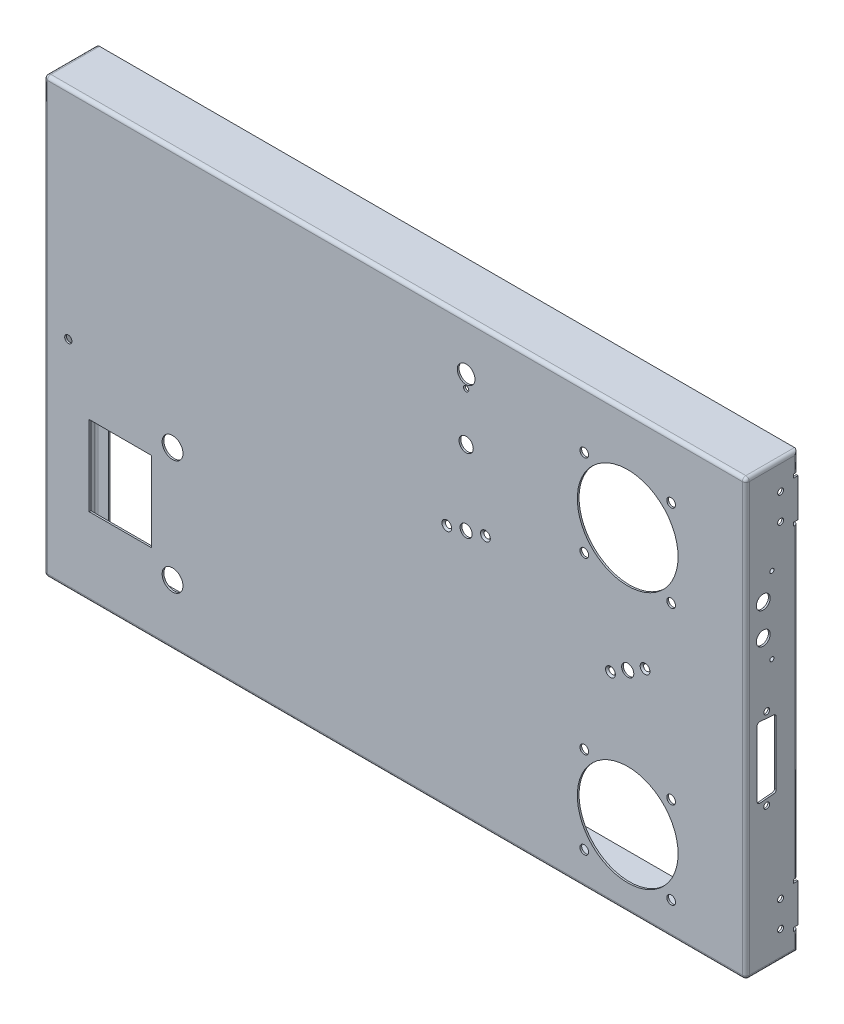
SolidWorks part; units mm, degrees
ref_plane "Спереди" through (0, 0, 0) normal (0, 0, 1) x (1, 0, 0)
ref_plane "Сверху" through (0, 0, 0) normal (0, 1, 0) x (1, 0, 0)
ref_plane "Справа" through (0, 0, 0) normal (1, 0, 0) x (0, 0, -1)
sketch "Эскиз1" plane through (0, 0, 0) normal (0, 0, 1) x (1, 0, 0)
  line L0 (-61.3968, 0) -> (71.7779, 0) construction
  line L1 (0, 39.2999) -> (0, -30.4018) construction
  line L2 (134, 171.767) -> (134, -149.1814) construction
  line L3 (-202, -125) -> (202, -125)
  line L4 (-202, -125) -> (-202, 125)
  line L5 (-202, 125) -> (202, 125)
  line L6 (202, -125) -> (202, 125)
  line L7 (38.5428, 67) -> (176.6445, 67) construction
  line L8 (42.9621, -81) -> (166.1488, -81) construction
  line L9 (-128, 10.4311) -> (-128, -100.5771) construction
  line L10 (117.5567, -13.5525) -> (151.8886, 6.269) construction
  line L11 (118.3296, -4) -> (150.7938, -4) construction
  line L12 (41, 146.2772) -> (41, -144.7589) construction
  line L13 (18.8787, 13.0871) -> (67.6345, 26.1512) construction
  line L14 (21.7516, 19) -> (64.0231, 19) construction
  line L15 (-220.928, 0) -> (-152.2094, 0) construction
  line L17 (-176, -80) -> (-140, -80)
  line L18 (-176, -80) -> (-176, -34)
  line L19 (-176, -34) -> (-140, -34)
  line L20 (-140, -80) -> (-140, -34)
  circle A0 centre (134, -4) radius 3.5
  circle A1 centre (-128, -24) radius 6
  circle A2 centre (-128, -90) radius 6
  circle A3 centre (134, 67) radius 29
  circle A4 centre (109, 92) radius 2.5
  circle A5 centre (109, 42) radius 2.5
  circle A6 centre (159, 42) radius 2.5
  circle A7 centre (159, 92) radius 2.5
  circle A8 centre (124.0664, -9.7942) radius 1.8
  circle A9 centre (143.985, 1.7058) radius 1.8
  circle A10 centre (134, -81) radius 29
  circle A11 centre (109, -56) radius 2.5
  circle A12 centre (159, -56) radius 2.5
  circle A13 centre (159, -106) radius 2.5
  circle A14 centre (109, -106) radius 2.5
  circle A15 centre (41, 97) radius 5.1
  circle A16 centre (41, 89.8) radius 1.5
  circle A17 centre (41, 62) radius 4.1
  circle A18 centre (41, 19) radius 3.5
  circle A19 centre (29.8882, 16.0371) radius 1.8
  circle A20 centre (52.1045, 21.99) radius 1.8
  circle A21 centre (-188, 0) radius 2.1
  dimension "D6" = 129
  dimension "D8" = 66
  dimension "D10" = 74
  dimension "D11" = 58
  dimension "D12" = 50
  dimension "D13" = 50
  dimension "D14" = 5
  dimension "D15" = 7
  dimension "D17" = 23
  dimension "D18" = 11.5
  dimension "D19" = 3.6
  dimension "D20" = 58
  dimension "D21" = 5
  dimension "D22" = 50
  dimension "D23" = 50
  dimension "D24" = 12
  dimension "D25" = 28
  dimension "D26" = 7.2
  dimension "D27" = 10.2
  dimension "D28" = 3
  dimension "D29" = 35
  dimension "D30" = 8.2
  dimension "D31" = 43
  dimension "D33" = 7
  dimension "D34" = 23
  dimension "D35" = 11.5
  dimension "D36" = 3.6
  dimension "D37" = 14
  dimension "D38" = 4.2
  dimension "D1" = 404
  dimension "D2" = 250
  dimension "D3" = 68
  dimension "D5" = 58
  dimension "D7" = 44
  dimension "D9" = 35
  dimension "D16" = 30
  dimension "D32" = 15
  dimension "D39" = 36
  dimension "D40" = 46
  dimension "D41" = 26
  dimension "D42" = 45
extrude "Вытянуть1" add sketch "Эскиз1" along normal blind 1
sketch "Эскиз2" plane through (0, 0, 1) normal (0, 0, 1) x (1, 0, 0)
  line L0 (-202, -125) -> (202, -125) construction
  line L1 (202, 125) -> (201, 125)
  line L2 (202, 125) -> (202, -125)
  line L3 (202, -125) -> (201, -125)
  line L4 (201, 125) -> (201, -125)
  line L5 (0, 139.8608) -> (0, -147.4853) construction
  line L6 (202, 125) -> (-202, 125) construction
  line L7 (-202, -125) -> (-201, -125)
  line L8 (-202, -125) -> (-202, 125)
  line L9 (-202, 125) -> (-201, 125)
  line L10 (-201, -125) -> (-201, 125)
  dimension "D1" = 1
  dimension "D2" = 1
extrude "Вытянуть2" add sketch "Эскиз2" against normal blind 30
sketch "Эскиз3" plane through (-202, 0, 0) normal (-1, 0, 0) x (0, 0, 1)
  line L0 (1, -125) -> (-29, -125) construction
  line L1 (-29, 125) -> (-28, 125)
  line L2 (-29, 125) -> (-29, -125)
  line L3 (-29, -125) -> (-28, -125)
  line L4 (-28, 125) -> (-28, -125)
  line L5 (27.4308, 0) -> (-48.9434, 0) construction
  line L7 (-29, 125) -> (-29, -125) construction
  dimension "D2" = 1
extrude "Вытянуть3" add sketch "Эскиз3" against normal blind 8
sketch "Эскиз4" plane through (202, 0, 0) normal (1, 0, 0) x (0, 0, -1)
  line L0 (28, -125) -> (28, 125) construction
  line L1 (28, -125) -> (28, 125)
  line L2 (29, -125) -> (28, -125) construction
  line L3 (29, -125) -> (28, -125)
  line L4 (28, 125) -> (29, 125) construction
  line L5 (28, 125) -> (29, 125)
  line L6 (29, -125) -> (29, 125) construction
  line L7 (29, -125) -> (29, 125)
extrude "Вытянуть4" add sketch "Эскиз4" against normal blind 8
sketch "Эскиз5" plane through (202, 0, 0) normal (1, 0, 0) x (0, 0, -1)
  line L0 (19, 62) -> (19, -138.3011) construction
  line L1 (-1, 62) -> (0, 62) construction
  line L3 (0, 0) -> (59.6299, 0) construction
  line L4 (-1, 0) -> (0, 0) construction
  line L5 (-1, -125) -> (29, -125) construction
  line L6 (11, 16.0371) -> (11, -70.1859) construction
  line L7 (-1, 16.0371) -> (0, 16.0371) construction
  line L8 (-18.6899, -20) -> (35.5426, -20) construction
  line L9 (-1, 125) -> (29, 125) construction
  line L10 (7.1358, 0.3513) -> (15.1358, -0.376)
  line L11 (9, 41) -> (9, 97) construction
  line L12 (5.5, -38.8575) -> (5.5, -1.1425)
  line L13 (-1, 97) -> (0, 97) construction
  line L14 (16.5, -38.1302) -> (16.5, -1.8698)
  line L15 (7.1358, -40.3513) -> (15.1358, -39.624)
  line L16 (9, 33) -> (9, 88.1289) construction
  line L17 (14, 72) -> (14, 29.1048) construction
  line L19 (-1, -125) -> (-1, 125) construction
  line L20 (29, -125) -> (29, 125) construction
  circle A0 centre (19, -109) radius 1.7
  circle A1 centre (19, 109) radius 1.7
  arc A2 (5.5, -1.1425) -> (7.1358, 0.3513) centre (7, -1.1425) cw
  arc A3 (15.1358, -0.376) -> (16.5, -1.8698) centre (15, -1.8698) cw
  arc A4 (7.1358, -40.3513) -> (5.5, -38.8575) centre (7, -38.8575) cw
  arc A5 (15.1358, -39.624) -> (16.5, -38.1302) centre (15, -38.1302) ccw
  circle A6 centre (11, 3.5) radius 1.7
  circle A7 centre (11, -43.5) radius 1.7
  circle A8 centre (9, 59) radius 4
  circle A9 centre (9, 41) radius 4
  circle A10 centre (14, 72) radius 1.2
  circle A11 centre (14, 28) radius 1.2
  circle A12 centre (19, -94) radius 1.7
  circle A13 centre (19, 94) radius 1.7
  point P31 (5.5, 0.5)
  point P34 (16.5, -0.5)
  point P37 (5.5, -40.5)
  point P40 (16.5, -39.5)
  dimension "D3" = 3.4
  dimension "D6" = 1.5
  dimension "D9" = 47
  dimension "D10" = 3.4
  dimension "D11" = 66
  dimension "D12" = 84
  dimension "D13" = 53
  dimension "D14" = 97
  dimension "D15" = 5
  dimension "D17" = 8
  dimension "D18" = 2.4
  dimension "D20" = 15
  dimension "D2" = 16
  dimension "D4" = 18
  dimension "D5" = 145
  dimension "D7" = 41
  dimension "D8" = 39
  dimension "D16" = 10
  dimension "D19" = 10
extrude "Вырез-Вытянуть1" cut sketch "Эскиз5" against normal blind 8
cosmetic thread "Условное изображение резьбы2" parameters "D1"=1, "D2"=3
cosmetic thread "Условное изображение резьбы3" parameters "D1"=1, "D2"=3
chamfer "Фаска2" distance 1 angle 45
sketch "Эскиз6" plane through (0, 0, 1) normal (0, 0, 1) x (1, 0, 0)
  line L0 (202, -125) -> (202, 125) construction
  line L1 (-202, 125) -> (202, 125)
  line L2 (-202, 125) -> (-202, 124)
  line L3 (-202, 124) -> (202, 124)
  line L4 (202, 125) -> (202, 124)
  line L5 (201, -125) -> (201, 125) construction
  line L6 (-202, -125) -> (201, -125)
  line L7 (-202, -125) -> (-202, -124)
  line L8 (-202, -124) -> (201, -124)
  line L9 (201, -125) -> (201, -124)
  dimension "D1" = 1
  dimension "D2" = 1
extrude "Вытянуть5" add sketch "Эскиз6" against normal up to surface (30 mm away)
fillet "Скругление1" radius 1
fillet "Скругление2" radius 2
sketch "Эскиз7" plane through (0, 0, -29) normal (0, 0, -1) x (-1, 0, 0)
  line L0 (0, 0) -> (-276.2699, 0) construction
  line L2 (-224.2324, -112) -> (-224.2324, -114)
  line L3 (-224.2324, -112) -> (-184.959, -112)
  line L4 (-224.2324, -114) -> (-184.959, -114)
  line L5 (-184.959, -112) -> (-184.959, -114)
  line L6 (-200, 125) -> (200, 125) construction
  line L7 (-224.2324, 112) -> (-184.959, 112)
  line L8 (-224.2324, 112) -> (-224.2324, 114)
  line L9 (-224.2324, 114) -> (-184.959, 114)
  line L10 (-184.959, 112) -> (-184.959, 114)
  line L11 (-184.959, -90) -> (-184.959, -88)
  line L12 (-224.2324, -90) -> (-184.959, -90)
  line L13 (-224.2324, -90) -> (-224.2324, -88)
  line L14 (-224.2324, -88) -> (-184.959, -88)
  line L15 (-229.2186, 101) -> (-174.091, 101) construction
  line L16 (-224.2324, 90) -> (-184.959, 90)
  line L17 (-184.959, 90) -> (-184.959, 88)
  line L18 (-224.2324, 88) -> (-184.959, 88)
  line L19 (-224.2324, 90) -> (-224.2324, 88)
  dimension "D1" = 11
  dimension "D2" = 2
  dimension "D3" = 26
extrude "Вырез-Вытянуть2" cut sketch "Эскиз7" against normal blind 2.5
sketch "Эскиз8" plane through (0, 0, -29) normal (0, 0, -1) x (-1, 0, 0)
  line L1 (-206.2638, 89.662) -> (-190.1585, 89.662)
  line L2 (-206.2638, 89.662) -> (-206.2638, 112.8311)
  line L3 (-206.2638, 112.8311) -> (-190.1585, 112.8311)
  line L4 (-190.1585, 89.662) -> (-190.1585, 112.8311)
  line L5 (-207.9189, -113.1276) -> (-187.4785, -113.1276)
  line L6 (-207.9189, -113.1276) -> (-207.9189, -88.8875)
  line L7 (-207.9189, -88.8875) -> (-187.4785, -88.8875)
  line L8 (-187.4785, -113.1276) -> (-187.4785, -88.8875)
extrude "Вырез-Вытянуть3" cut sketch "Эскиз8" against normal blind 2
sketch "Эскиз9" plane through (0, 0, -27) normal (0, 0, -1) x (-1, 0, 0)
  line L4 (-202, 112) -> (-202, 90)
  line L5 (-202, 90) -> (-201, 90)
  line L6 (-201, 90) -> (-201, 112)
  line L7 (-201, 112) -> (-202, 112)
  line L8 (-202, 112) -> (-202, 90)
  line L9 (-202, 90) -> (-201, 90)
  line L10 (-201, 90) -> (-201, 112)
  line L11 (-201, 112) -> (-202, 112)
  line L12 (-202, -112) -> (-201, -112)
  line L13 (-202, -112) -> (-201, -112)
  line L14 (-201, -112) -> (-201, -90)
  line L15 (-201, -112) -> (-201, -90)
  line L16 (-202, -90) -> (-202, -112)
  line L17 (-202, -90) -> (-202, -112)
  line L18 (-201, -90) -> (-202, -90)
  line L19 (-201, -90) -> (-202, -90)
  dimension "D1" = 0
  dimension "D2" = 0
extrude "Вытянуть6" add sketch "Эскиз9" along normal up to surface (2 mm away)
sketch "Эскиз10" plane through (201, 0, 0) normal (-1, 0, 0) x (0, 0, 1)
  circle A0 centre (-14, 28) radius 2.5
  circle A1 centre (-14, 72) radius 2.5
  circle A3 centre (-14, 72) radius 1.2 construction
  circle A4 centre (-14, 72) radius 1.2
  circle A5 centre (-14, 28) radius 1.2 construction
  circle A6 centre (-14, 28) radius 1.2
  dimension "D1" = 5
extrude "Вытянуть7" add sketch "Эскиз10" along normal blind 1.5
